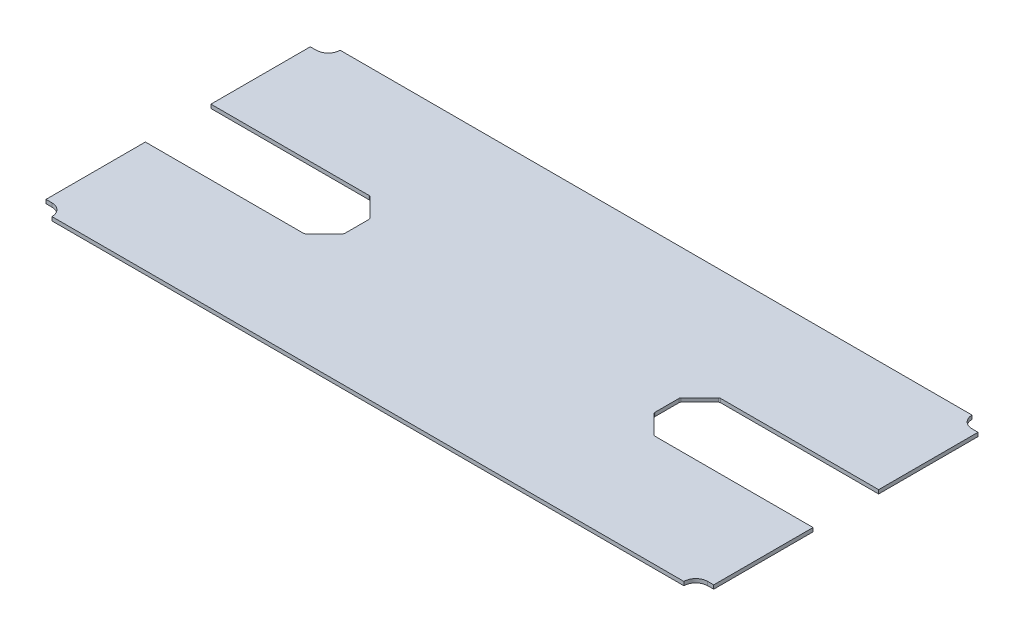
SolidWorks part; units mm, degrees
material "Mahogany"
ref_plane "Front Plane" through (0, 0, 0) normal (0, 0, 1) x (1, 0, 0)
ref_plane "Top Plane" through (0, 0, 0) normal (0, 1, 0) x (1, 0, 0)
ref_plane "Right Plane" through (0, 0, 0) normal (1, 0, 0) x (0, 0, -1)
sketch "Sketch1" plane through (0, 0, 0) normal (0, 1, 0) x (1, 0, 0)
  line L0 (-840, 82.5) -> (-390, 82.5)
  line L1 (-840, 362.5) -> (840, 362.5)
  line L2 (-840, 362.5) -> (-840, -362.5)
  line L3 (-840, -362.5) -> (840, -362.5)
  line L4 (840, 362.5) -> (840, -362.5)
  line L5 (-840, 362.5) -> (840, -362.5) construction
  line L6 (-840, -362.5) -> (840, 362.5) construction
  line L23 (-390, 82.5) -> (-390, -82.5)
  line L24 (-390, -82.5) -> (-840, -82.5)
  line L25 (840, 82.5) -> (390, 82.5)
  line L26 (390, 82.5) -> (390, -82.5)
  line L27 (390, -82.5) -> (840, -82.5)
  line L28 (-840, 332.5) -> (-825, 332.5)
  line L29 (0, -362.5) -> (0, 362.5) construction
  line L30 (-840, 0) -> (840, 0) construction
  line L31 (-840, -332.5) -> (-825, -332.5)
  line L32 (840, 332.5) -> (825, 332.5)
  line L33 (840, -332.5) -> (825, -332.5)
  arc A0 (-825, 332.5) -> (-795, 362.5) centre (-825, 362.5) ccw
  arc A1 (-825, -332.5) -> (-795, -362.5) centre (-825, -362.5) cw
  arc A2 (825, 332.5) -> (795, 362.5) centre (825, 362.5) cw
  arc A3 (825, -332.5) -> (795, -362.5) centre (825, -362.5) ccw
  point P0 (0, 0)
  point P26 (390, 0)
  point P27 (-390, 0)
  dimension "D6" = 30
  dimension "D4" = 450
  dimension "D5" = 165
  dimension "D2" = 725
  dimension "D1" = 1680
  dimension "D3" = 15
extrude "Boss-Extrude1" add sketch "Sketch1" along normal blind 9.525 contours L27 L26 L25 L4 L1 L2 L0 L23 L24 L3 region at (0, 0, 0)
chamfer "Chamfer1" distance 50 angle 45 4 edges at (390, 4.7625, 82.5) (390, 4.7625, -82.5) (-390, 4.7625, 82.5) (-390, 4.7625, -82.5)
fillet "Fillet2" radius 5 8 edges at (390, 4.7625, -32.5) (390, 4.7625, 32.5) (440, 4.7625, 82.5) (440, 4.7625, -82.5) (-440, 4.7625, 82.5) (-390, 4.7625, 32.5) (-390, 4.7625, -32.5) (-440, 4.7625, -82.5)
equation "\"W\"= 1700"
equation "\"L\"= 760"
equation "\"H\"= 810"
equation "\"ARM_BOLT_SPACING\"= 140"
equation "\"ARM_TO_WALL\"= 300"
equation "\"D4@Sketch1\"=\"ARM_TO_WALL\"+\"ARM_BOLT_SPACING\"+10"
equation "\"D5@Sketch1\"=\"ARM_BOLT_SPACING\"+25"
equation "\"D2@Sketch1\"=\"L\"-35"
equation "\"D1@Sketch1\"=\"W\"-20"
